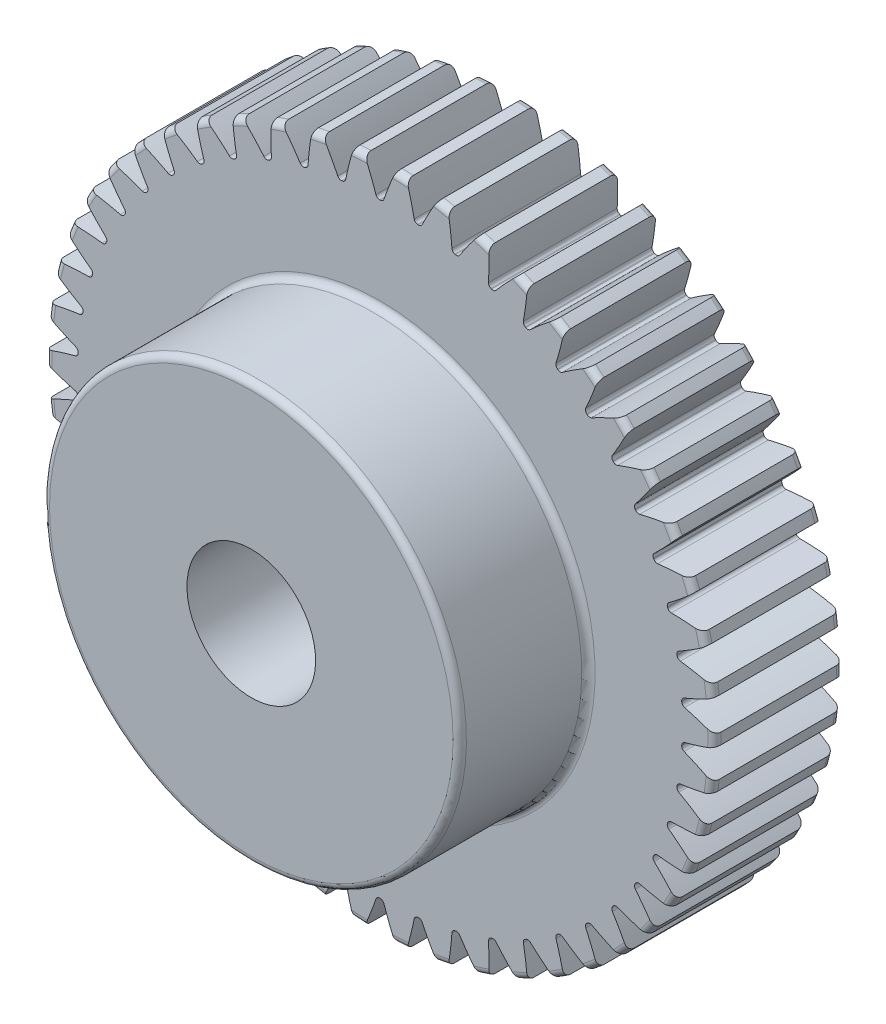
SolidWorks part; units mm, degrees
ref_plane "Front Plane" through (0, 0, 0) normal (0, 0, 1) x (1, 0, 0)
ref_plane "Top Plane" through (0, 0, 0) normal (0, 1, 0) x (1, 0, 0)
ref_plane "Right Plane" through (0, 0, 0) normal (1, 0, 0) x (0, 0, -1)
sketch "Sketch1" plane through (0, 0, 0) normal (0, 0, 1) x (1, 0, 0)
  line L0 (-635, 0) -> (635, 0) construction
  circle A0 centre (0, 0) radius 33.02 construction
  circle A1 centre (0, 0) radius 31.75 construction
  circle A2 centre (0, 0) radius 29.845 construction
  circle A3 centre (0, 0) radius 20.574 construction
  circle A4 centre (0, 0) radius 6.35 construction
  dimension "D1" = 3.175
  dimension "OD" = 66.04
  dimension "Pitch Dia." = 63.5
  dimension "D2" = 1.27
  dimension "D3" = 3.175
  dimension "Root Dia." = 59.69
  dimension "Hub Dia." = 41.148
  dimension "Shaft Dia." = 12.7
  dimension "Number of Teeth" = 1270
sketch "Sketch2" plane through (0, 0, 0) normal (1, 0, 0) x (0, 0, -1)
  line L0 (0, 0) -> (-12.7, 0) construction
  line L1 (-12.7, 0) -> (-25.4, 0) construction
  dimension "Overall Width" = 25.4
  dimension "Face Width" = 12.7
sketch "Sketch4" plane through (0, 0, 0) normal (1, 0, 0) x (0, 0, -1)
  line L0 (-25.4, 6.35) -> (-25.4, 20.574)
  line L1 (-25.4, 20.574) -> (-12.7, 20.574)
  line L2 (-12.7, 20.574) -> (-12.7, 33.02)
  line L3 (-12.7, 33.02) -> (0, 33.02)
  line L4 (0, 33.02) -> (0, 6.35)
  line L5 (-12.7, 20.574) -> (-12.7, 0) construction
  line L6 (0, 33.02) -> (0, -33.02) construction
  line L7 (-12.7, 20.574) -> (0, 20.574) construction
  line L12 (-25.4, 6.35) -> (0, 6.35)
revolve "Revolve1" add sketch "Sketch4" angle 360 about L1
fillet "Fillet2" radius 0.6604 4 edges at (0, 20.574, 25.4) (0, 20.574, 12.7) (0, 33.02, 12.7) (0, 33.02, 0)
sketch "Sketch7" plane through (0, 0, 12.7) normal (0, 0, 1) x (1, 0, 0)
  line L0 (0, 0) -> (0, 33.02) construction
  line L1 (0.9973, 31.7343) -> (1.4979, 32.986) construction
  line L3 (2.0733, 32.9548) -> (1.9936, 31.6873) construction
  line L4 (1.9936, 31.6873) -> (1.874, 29.7861) construction
  line L5 (0, 0) -> (1.874, 29.7861) construction
  line L6 (0.9973, 31.7343) -> (0, 0) construction
  line L7 (0.9973, 31.7343) -> (1.0372, 33.0037) construction
  line L8 (0.9973, 31.7343) -> (0, 0) construction
  circle A0 centre (0, 0) radius 33.02 construction
  arc A1 (-0.035, 29.845) -> (0.035, 29.845) centre (0, 0) cw
  circle A2 centre (0, 0) radius 29.845 construction
  arc A3 (-0.9973, 31.7343) -> (0.9973, 31.7343) centre (0, 0) cw construction
  circle A4 centre (0, 0) radius 31.75 construction
  arc A5 (2.6175, 32.9161) -> (1.5287, 32.9846) centre (0, 0) ccw construction
  arc A6 (0.9973, 31.7343) -> (2.9879, 31.6091) centre (0, 0) cw construction
  arc A7 (-1.5287, 32.9846) -> (1.5287, 32.9846) centre (0, 0) cw
  arc A8 (0.3964, 30.1041) -> (1.5287, 32.9846) centre (30.4767, 19.9434) cw
  arc A9 (-0.3964, 30.1041) -> (-1.5287, 32.9846) centre (-30.4767, 19.9434) ccw
  arc A10 (-0.035, 29.845) -> (-0.3964, 30.1041) centre (-0.0354, 30.226) cw
  arc A11 (0.035, 29.845) -> (0.3964, 30.1041) centre (0.0354, 30.226) ccw
  point P26 (-0.3096, 29.8434)
  point P29 (0.3096, 29.8434)
  dimension "D4" = 0.381
  dimension "D5" = 31.75
  dimension "D2" = 1.9949
  dimension "D1" = 3.9898
  dimension "D3" = 20
extrude "Cut-Extrude2" cut sketch "Sketch7" against normal through all
pattern_circular "CirPattern1" count 50 over 360 about axis through (0, 0, 25.4) along (0, 0, -1) of "Cut-Extrude2"
equation "\"D1@Sketch1\"=2.5*(\"Pitch Dia.@Sketch1\"/\"Number of Teeth@Sketch1\")"
equation "\"D1@CirPattern1\"=\"Number of Teeth@Sketch1\""
equation "\"D1@Fillet2\"=\"OD@Sketch1\"*.01"
equation "\"D1@Sketch7\"=3.14159*(\"Pitch Dia.@Sketch1\"/\"Number of Teeth@Sketch1\")"
equation "\"D2@Sketch7\"=\"D1@Sketch7\"/2"
equation "\"D4@Sketch7\"=\"D1@Sketch7\"*.0955"
equation "\"D5@Sketch7\"=\"Pitch Dia.@Sketch1\"/2"
